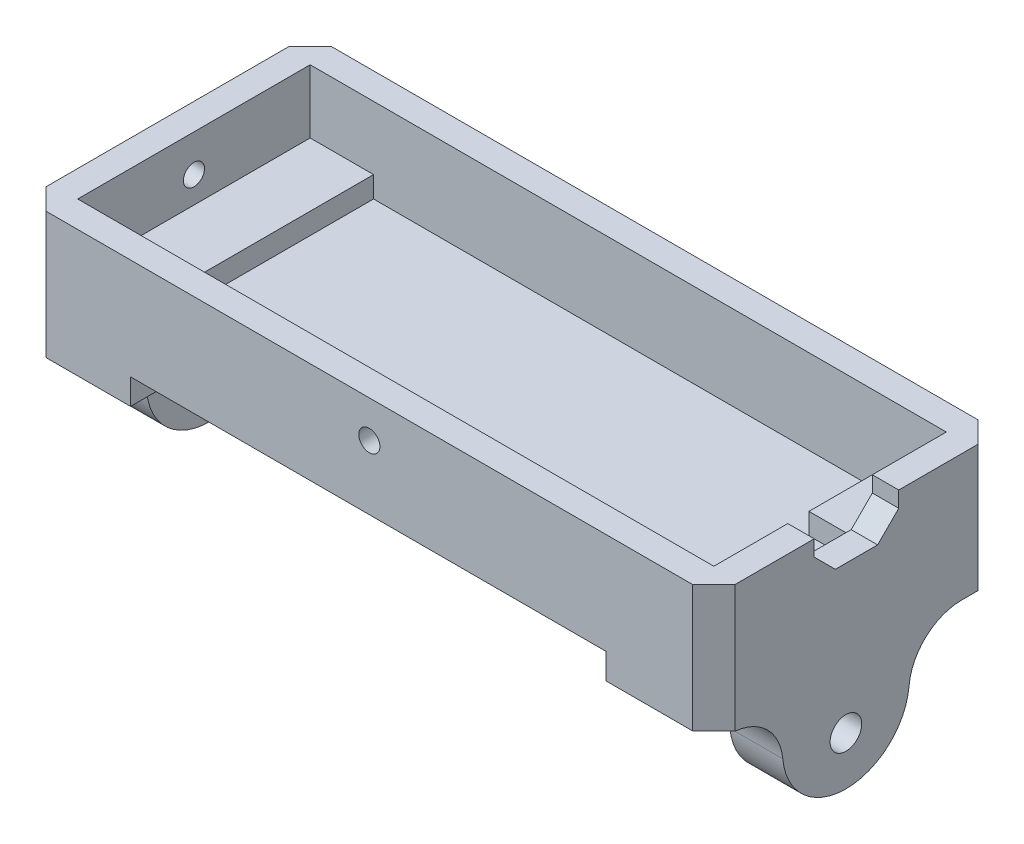
SolidWorks part; units mm, degrees
ref_plane "Front Plane" through (0, 0, 0) normal (0, 0, 1) x (1, 0, 0)
ref_plane "Top Plane" through (0, 0, 0) normal (0, 1, 0) x (1, 0, 0)
ref_plane "Right Plane" through (0, 0, 0) normal (1, 0, 0) x (0, 0, -1)
sketch "Sketch1" plane through (0, 0, 0) normal (0, 1, 0) x (1, 0, 0)
  line L0 (-19, 11.7194) -> (-29, 6.7194)
  line L1 (-19, 11.7194) -> (-10, 11.7194)
  line L2 (-29, 6.7194) -> (-29, -3.2806)
  line L3 (-19, -9.2806) -> (21, -9.2806)
  line L4 (29, 7.4633) -> (29, -6.3504)
  line L5 (-19, -9.2806) -> (-29, -3.2806)
  line L6 (-10, 11.7194) -> (-9.4845, 10.9718)
  line L7 (-9.0728, 10.7556) -> (-6.9671, 10.7556)
  line L8 (-6.5657, 10.9575) -> (-6, 11.7194)
  line L9 (-6, 11.7194) -> (19, 11.7194)
  line L10 (19, 11.7194) -> (19, 4.7194)
  line L11 (23, 4.7194) -> (23, 8.7194)
  line L12 (23, 8.7194) -> (27.7439, 8.7194)
  line L13 (27.7439, 8.7194) -> (29, 7.4633)
  line L14 (29, -6.3504) -> (21, -9.2806)
  line L15 (-29.7, 12.2194) -> (30.5, 12.2194)
  line L16 (-30.2, 14.7194) -> (31, 14.7194)
  line L17 (-32.2, 12.7194) -> (-32.2, -10.2806)
  line L18 (-30.2, -12.2806) -> (31, -12.2806)
  line L19 (33, 12.7194) -> (33, -10.2806)
  line L20 (30.5, 12.2194) -> (30.5, -9.7806)
  line L21 (-29.7, -9.7806) -> (30.5, -9.7806)
  line L22 (-29.7, 12.2194) -> (-29.7, -9.7806)
  line L23 (-30.2, -12.2806) -> (-32.2, -10.2806)
  line L24 (-32.2, 12.7194) -> (-30.2, 14.7194)
  line L25 (31, 14.7194) -> (33, 12.7194)
  line L26 (31, -12.2806) -> (33, -10.2806)
  arc A0 (-6.9671, 10.7556) -> (-6.5657, 10.9575) centre (-6.9671, 11.2556) ccw
  arc A1 (-9.4845, 10.9718) -> (-9.0728, 10.7556) centre (-9.0728, 11.2556) ccw
  arc A2 (19, 4.7194) -> (23, 4.7194) centre (21, 4.7194) ccw
  arc A7 (30.5, 12.2194) -> (30.5, 12.2194) centre (30.5, 12.2194) cw
  arc A8 (30.5, -9.7806) -> (30.5, -9.7806) centre (30.5, -9.7806) ccw
  arc A9 (-29.7, -9.7806) -> (-29.7, -9.7806) centre (-29.7, -9.7806) ccw
  arc A10 (-29.7, 12.2194) -> (-29.7, 12.2194) centre (-29.7, 12.2194) ccw
  arc A11 (-32.2, -10.2806) -> (-30.2, -12.2806) centre (-30.2, -10.2806) ccw construction
  arc A12 (-30.2, 14.7194) -> (-32.2, 12.7194) centre (-30.2, 12.7194) ccw construction
  arc A13 (31, -12.2806) -> (33, -10.2806) centre (31, -10.2806) ccw construction
  arc A14 (31, 14.7194) -> (33, 12.7194) centre (31, 12.7194) cw construction
  point P0 (0, 3.1087)
  point P7 (-10, 11.7194)
  point P8 (-6, 11.7194)
  point P17 (19, 11.7194)
  dimension "D7" = 0.5
  dimension "D1" = 10
  dimension "D2" = 5
  dimension "D3" = 10
  dimension "D4" = 3.2
  dimension "D5" = 4
  dimension "D6" = 9
  dimension "D8" = 25
  dimension "D9" = 7
  dimension "D10" = 4
  dimension "D11" = 4
  dimension "D12" = 21
  dimension "D13" = 4
  dimension "D14" = 3
  dimension "D15" = 3
  dimension "D17" = 2.5
extrude "Boss-Extrude1" add sketch "Sketch1" along normal blind 10 contours L16 L24 L17 L23 L18 L26 L19 L25 L22 L15 L20 L21 region at (0.4, 0, -14.0137)
extrude "Boss-Extrude2" add sketch "Sketch1<3>" along normal blind 2 contours L15 L22 L21 L20 L10 A2 L11 L12 L13 L4 L14 L3 L5 L2 L0 L1 L6 A1 L7 A0 L8 L9 | A2 L10 L9 L8 A0 L7 A1 L6 L1 L0 L2 L5 L3 L14 L4 L13 L12 L11 region at (-0.075, 0, -0.9762) region at (0.4, 0, -12.1553)
sketch "Sketch1<3>" plane through (0, 0, 0) normal (0, 1, 0) x (1, 0, 0) same geometry as "Sketch1"
sketch "Sketch2" plane through (0, 2, 0) normal (0, 1, 0) x (1, 0, 0)
  line L0 (-29.7, -9.7806) -> (30.5, -9.7806) construction
  line L1 (-29.7, 12.2194) -> (-23.7, 12.2194)
  line L2 (-29.7, 12.2194) -> (-29.7, -9.7806)
  line L3 (-29.7, -9.7806) -> (-23.7, -9.7806)
  line L4 (-23.7, 12.2194) -> (-23.7, -9.7806)
  line L5 (-29.7, -9.7806) -> (30.5, -9.7806) construction
  line L6 (30.5, 12.2194) -> (24.5, 12.2194)
  line L7 (30.5, 12.2194) -> (30.5, -9.7806)
  line L8 (30.5, -9.7806) -> (24.5, -9.7806)
  line L9 (24.5, 12.2194) -> (24.5, -9.7806)
  dimension "D1" = 6
  dimension "D2" = 6
extrude "Boss-Extrude3" add sketch "Sketch2" along normal blind 2
sketch "Sketch3" plane through (0, 0, 0) normal (0, -1, 0) x (1, 0, 0)
  line L0 (-30.2, 12.2806) -> (31, 12.2806) construction
  line L1 (-32.2, 14.2806) -> (36, 14.2806)
  line L2 (-37.2, 9.2806) -> (-37.2, -11.7194)
  line L3 (-32.2, -16.7194) -> (36, -16.7194)
  line L4 (41, 9.2806) -> (41, -11.7194)
  line L5 (-30.2, -14.7194) -> (31, -14.7194) construction
  line L6 (-32.2, -12.7194) -> (-32.2, 10.2806) construction
  line L7 (33, -12.7194) -> (33, 10.2806) construction
  line L8 (-37.2, 9.2806) -> (-32.2, 14.2806)
  line L9 (-37.2, -11.7194) -> (-32.2, -16.7194)
  line L10 (36, 14.2806) -> (41, 9.2806)
  line L11 (36, -16.7194) -> (41, -11.7194)
  point P0 (-37.2, 14.2806)
  point P1 (41, -16.7194)
  point P2 (-37.2, -16.7194)
  point P3 (41, 14.2806)
  dimension "D1" = 2
  dimension "D2" = 2
  dimension "D3" = 5
  dimension "D4" = 8
extrude "Boss-Extrude4" add sketch "Sketch3" along normal blind 2
fillet "Fillet1" radius 0.5 2 edges at (32, 0, -13.7194) (0.4, 0, -14.7194)
sketch "Sketch4" plane through (33, 0, 0) normal (1, 0, 0) x (0, 0, -1)
  line L0 (12.7194, 10) -> (-10.2806, 10) construction
  line L1 (-2.7806, 10) -> (5.2194, 10)
  line L2 (-2.7806, 10) -> (-2.7806, 8.5)
  line L3 (-0.7806, 6.5) -> (3.2194, 6.5)
  line L4 (5.2194, 10) -> (5.2194, 8.5)
  line L7 (-2.7806, 8.5) -> (-0.7806, 6.5)
  line L8 (3.2194, 6.5) -> (5.2194, 8.5)
  line L9 (-12.2806, 10) -> (14.7194, 10) construction
  line L10 (14.7194, 10) -> (12.7194, 10) construction
  line L11 (-12.2806, 10) -> (-12.2806, 0) construction
  point P1 (5.2194, 6.5)
  point P2 (-2.7806, 6.5)
  dimension "D2" = 8
  dimension "D3" = 3.5
  dimension "D4" = 9.5
extrude "Cut-Extrude1" cut sketch "Sketch4" against normal blind 10.5
sketch "Sketch5" plane through (0, 0, 0) normal (0, 1, 0) x (-1, 0, 0)
  line L0 (-40.124, 15.07) -> (-40.124, -12.93) construction
  line L1 (-33, 13.7806) -> (-38, 13.7806)
  line L2 (-33, 13.7806) -> (-33, 4.7806)
  line L3 (-33, 4.7806) -> (-38, 4.7806)
  line L4 (-38, 13.7806) -> (-38, 4.7806)
  line L5 (-33, -14.2194) -> (-38, -14.2194)
  line L6 (-33, -14.2194) -> (-33, -5.2194)
  line L7 (-33, -5.2194) -> (-38, -5.2194)
  line L8 (-38, -14.2194) -> (-38, -5.2194)
  line L10 (-36, 14.2806) -> (32.2, 14.2806) construction
  line L11 (-33, 2.7806) -> (-33, 10.2806) construction
  line L12 (-33, -13.4265) -> (-33, 10.2806) construction
  point P12 (-36, 14.2806)
  dimension "D1" = 9
  dimension "D2" = 28
  dimension "D3" = 9
  dimension "D4" = 5
  dimension "D5" = 5
  dimension "D6" = 28
  dimension "D7" = 31
  dimension "D8" = 0.5
extrude "Boss-Extrude5" add sketch "Sketch5" along normal blind 5
sketch "Sketch7" plane through (38, 0, 0) normal (1, 0, 0) x (0, 0, -1)
  line L1 (-13.7806, 5) -> (-10.2806, 5)
  line L2 (-13.7806, 5) -> (-13.7806, 0)
  line L3 (-13.7806, 0) -> (-10.2806, 0)
  line L4 (-10.2806, 5) -> (-10.2806, 0)
  line L5 (15.2194, 5) -> (12.7194, 5)
  line L6 (15.2194, 5) -> (15.2194, 0)
  line L7 (15.2194, 0) -> (12.7194, 0)
  line L8 (12.7194, 5) -> (12.7194, 0)
extrude "Cut-Extrude3" cut sketch "Sketch7" against normal blind 5
sketch "Sketch10" plane through (0, 0, -12.7194) normal (0, 0, -1) x (-1, 0, 0)
  line L0 (-35.5, 5) -> (-35.5, 2.5) construction
  line L5 (-38, 5) -> (-33, 5)
  line L6 (-38, 5) -> (-38, 0)
  line L7 (-38, 0) -> (-33, 0)
  line L8 (-33, 5) -> (-33, 0)
  line L9 (-35.5, 2.5) -> (-38, 2.5) construction
  circle A0 centre (-35.5, 2.5) radius 1.5
  circle A1 centre (-35.5, 2.5) radius 2.5
  line M1 (-38, 5) -> (-38, 0)
  line M2 (-38, 0) -> (-33, 0)
  dimension "D1" = 3
extrude "Cut-Extrude4" cut sketch "Sketch10" against normal up to surface (23 mm away) contours A0 L5 M1 | A0 L6 M2 region at (37.4416, 4.4416, -12.7194) region at (37.4416, 0.5584, -12.7194) up to face at (35.5, 2.5, 10.2806)
sketch "Sketch11" plane through (0, 0, -12.7194) normal (0, 0, -1) x (-1, 0, 0)
  circle A0 centre (-35.5, 2.5) radius 1.5
  dimension "D1" = 3
extrude "Cut-Extrude5" cut sketch "Sketch11" against normal up to surface (23 mm away) up to face at (34.875, 2.5, 10.2806)
sketch "Sketch12" plane through (-32.2, 0, 0) normal (-1, 0, 0) x (0, 0, 1)
  line L0 (14.2806, -2) -> (14.2806, 2.4239)
  line L1 (14.2806, 2.4239) -> (9.8567, -2)
  line L2 (14.2806, -2) -> (9.2806, -2) construction
  line L3 (9.8567, -2) -> (14.2806, -2)
  line L4 (-1.2194, -2) -> (-1.2194, 8.8282) construction
  line L5 (9.2806, -2) -> (-11.7194, -2) construction
  line L6 (-12.2955, -2) -> (-16.7194, -2)
  line L7 (-16.7194, -2) -> (-16.7194, 2.4239)
  line L8 (-16.7194, 2.4239) -> (-12.2955, -2)
extrude "Cut-Extrude6" cut sketch "Sketch12" against normal blind 45 from offset 10 offset against normal yes
sketch "Sketch13" plane through (0, 4, 0) normal (0, 1, 0) x (1, 0, 0)
  line L0 (24.5, 12.2194) -> (24.5, -9.7806) construction
  line L1 (30.5, 5.2194) -> (24.5, 5.2194)
  line L2 (30.5, 5.2194) -> (30.5, -2.8008)
  line L3 (30.5, -2.8008) -> (24.5, -2.8008)
  line L4 (24.5, 5.2194) -> (24.5, -2.8008)
extrude "Cut-Extrude7" cut sketch "Sketch13" against normal up to surface (2 mm away) up to face at (0.4, 2, -1.2194)
sketch "Sketch19" plane through (-32.2, 0, 0) normal (-1, 0, 0) x (0, 0, 1)
  line L0 (-12.7194, 0) -> (10.2806, 0) construction
  circle A0 centre (-1.2194, 6.5) radius 1
  dimension "D1" = 2
  dimension "D2" = 6.5
extrude "Cut-Extrude9" cut sketch "Sketch19" against normal blind 6
sketch "Sketch20" plane through (0, 0, 12.2806) normal (0, 0, 1) x (1, 0, 0)
  line L0 (-22.2, 0.4239) -> (22.8, 0.4239) construction
  line L1 (0.4, 10) -> (0.4, 3.6445) construction
  line L2 (-30.2, 10) -> (31, 10) construction
  circle A0 centre (0.4, 6.5039) radius 1
  dimension "D1" = 2
  dimension "D2" = 6.08
extrude "Cut-Extrude10" cut sketch "Sketch20" against normal blind 6
sketch "Sketch21" plane through (0, 0, 0) normal (0, 1, 0) x (1, 0, 0)
  line L0 (33, 12.7194) -> (33, -10.2806)
  line L1 (41, 11.7194) -> (41, -9.2806)
  line L2 (22.8, 15.2194) -> (22.8, 14.7245)
  line L3 (22.8, 14.7245) -> (31, 14.7194)
  line L4 (31, 14.7194) -> (33, 12.7194)
  line L5 (-22.2, 15.2194) -> (-22.2, 14.7245)
  line L6 (-22.2, 14.7245) -> (-30.2, 14.7194)
  line L12 (-22.2, -14.2806) -> (-22.2, -12.2806)
  line L13 (-22.2, -12.2806) -> (-30.2, -12.2806)
  line L14 (-22.2, -12.2806) -> (-30.2, -12.2806)
  line L15 (-30.2, -12.2806) -> (-32.2, -10.2806)
  line L16 (-30.2, -12.2806) -> (-32.2, -10.2806)
  line L17 (-32.2, -10.2806) -> (-32.2, 12.7194)
  line L18 (-22.2, 15.2194) -> (-22.2, 16.7194)
  line L19 (-22.2, 16.7194) -> (-32.2, 16.7194)
  line L20 (-32.2, 16.7194) -> (-37.2, 11.7194)
  line L21 (-37.2, 11.7194) -> (-37.2, -9.2806)
  line L22 (-37.2, -9.2806) -> (-32.2, -14.2806)
  line L23 (-32.2, -14.2806) -> (-22.2, -14.2806)
  line L24 (-22.2, -14.2806) -> (-22.2, -12.2806)
  line L30 (-22.2, 15.2194) -> (-22.2, 16.7194)
  line L31 (-22.2, 16.7194) -> (-32.2, 16.7194)
  line L32 (-32.2, 16.7194) -> (-37.2, 11.7194)
  line L33 (-37.2, 11.7194) -> (-37.2, -9.2806)
  line L34 (-37.2, -9.2806) -> (-32.2, -14.2806)
  line L35 (-32.2, -14.2806) -> (-22.2, -14.2806)
  line L43 (31, -12.2806) -> (22.8, -12.2806)
  line L44 (22.8, -12.2806) -> (22.8, -14.2806)
  line L45 (22.8, -14.2806) -> (36, -14.2806)
  line L46 (36, -14.2806) -> (41, -9.2806)
  line L47 (41, -9.2806) -> (41, 11.7194)
  line L48 (41, 11.7194) -> (36, 16.7194)
  line L49 (36, 16.7194) -> (22.8, 16.7194)
  line L50 (22.8, 16.7194) -> (22.8, 15.2194)
  line L51 (31, -12.2806) -> (22.8, -12.2806)
  line L52 (22.8, 15.2194) -> (31.2071, 15.2194)
  line L53 (31.2071, 15.2194) -> (33, 13.4265)
  line L54 (33, 13.4265) -> (33, 12.7194)
  line L55 (33, 12.7194) -> (35.5, 12.7194)
  line L56 (35.5, 12.7194) -> (35.5, 5.2194)
  line L58 (35.5, 5.2194) -> (33, 5.2194)
  line L59 (33, 5.2194) -> (33, -4.7806)
  line L60 (33, 5.2194) -> (33, -4.7806)
  line L61 (33, -4.7806) -> (35.5, -4.7806)
  line L63 (22.8, -12.2806) -> (22.8, -14.2806)
  line L64 (22.8, -14.2806) -> (36, -14.2806)
  line L65 (36, -14.2806) -> (41, -9.2806)
  line L67 (41, 11.7194) -> (36, 16.7194)
  line L68 (36, 16.7194) -> (22.8, 16.7194)
  line L69 (22.8, 16.7194) -> (22.8, 15.2194)
  line L81 (-32.2, -10.2806) -> (-32.2, 12.7194)
  line L82 (-32.2, 12.7194) -> (-29.7, 15.2194)
  line L83 (-32.2, 12.7194) -> (-29.7, 15.2194)
  line L84 (-29.7, 15.2194) -> (-22.2, 15.2194)
  line L92 (35.5, -4.7806) -> (35.5, -10.2806)
  line L93 (35.5, -10.2806) -> (33, -10.2806)
  line L94 (33, -10.2806) -> (31, -12.2806)
  line L95 (33, -10.2806) -> (31, -12.2806)
  line M32 (-22.2, -14.2806) -> (-22.2, -12.2806)
  line M33 (-22.2, -12.2806) -> (-30.2, -12.2806)
  line M34 (-30.2, -12.2806) -> (-32.2, -10.2806)
  line M35 (-32.2, -10.2806) -> (-32.2, 12.7194)
  line M36 (-32.2, 12.7194) -> (-29.7, 15.2194)
  line M37 (-29.7, 15.2194) -> (-22.2, 15.2194)
  line M38 (-22.2, 15.2194) -> (-22.2, 16.7194)
  line M39 (-22.2, 16.7194) -> (-32.2, 16.7194)
  line M40 (-32.2, 16.7194) -> (-37.2, 11.7194)
  line M41 (-37.2, 11.7194) -> (-37.2, -9.2806)
  line M42 (-37.2, -9.2806) -> (-32.2, -14.2806)
  line M43 (-32.2, -14.2806) -> (-22.2, -14.2806)
  dimension "D1" = 0
  dimension "D2" = 0
extrude "Cut-Extrude13" cut sketch "Sketch21" against normal blind 23 and the other way blind 23 contours M43 M32 M33 M34 M35 M36 M37 M38 M39 M40 M41 M42 | L6 L5 M37 M36 | L0 L95 L51 L63 L64 L65 L1 L67 L68 L69 L2 L3 L4 region at (34.25, 0, -8.9694) region at (28.2069, 0, -14.7374) region at (35.6486, 0, -0.7875) region at (34.25, 0, 7.5306) region at (-32.9361, 0, -0.9063) region at (-26.0827, 0, -14.968)
sketch "Sketch24" plane through (0, -2, 0) normal (0, -1, 0) x (1, 0, 0)
  line L0 (-32.2, -0.2194) -> (33, -0.2194) construction
  line L1 (33, 10.2806) -> (33, -12.7194) construction
  line L2 (-32.2, -12.7194) -> (-32.2, 10.2806) construction
  line L3 (-32.2, 5.7806) -> (-27.2, 5.7806)
  line L4 (-32.2, 5.7806) -> (-32.2, -6.2194)
  line L5 (-32.2, -6.2194) -> (-27.2, -6.2194)
  line L6 (-27.2, 5.7806) -> (-27.2, -6.2194)
  line L8 (33, 5.7806) -> (28, 5.7806)
  line L9 (33, 5.7806) -> (33, -6.2194)
  line L10 (33, -6.2194) -> (28, -6.2194)
  line L11 (28, 5.7806) -> (28, -6.2194)
  dimension "D1" = 65.2
  dimension "D2" = 5
  dimension "D3" = 5
  dimension "D4" = 12
  dimension "D5" = 6
  dimension "D6" = 6
  dimension "D7" = 12
extrude "Boss-Extrude6" add sketch "Sketch24" along normal blind 10
fillet "Fillet2" radius 6 4 edges at (30.5, -12, -6.2194) (30.5, -12, 5.7806) (-29.7, -12, 5.7806) (-29.7, -12, -6.2194)
sketch "Sketch25" plane through (-32.2, 0, 0) normal (-1, 0, 0) x (0, 0, 1)
  line L0 (-0.2194, -12) -> (-0.2194, -3.1317) construction
  circle A0 centre (-0.2194, -7.409) radius 1.5
  dimension "D1" = 3
extrude "Cut-Extrude14" cut sketch "Sketch25" against normal through all
fillet "Fillet3" radius 5 4 edges at (30.5, -2, 5.7806) (-29.7, -2, 5.7806) (-29.7, -2, -6.2194) (30.5, -2, -6.2194)
sketch "Sketch26" plane through (0, 10, 0) normal (0, 1, 0) x (1, 0, 0)
  line L16 (33, -2.7806) -> (30.5, -2.7806)
  line L17 (30.5, -2.7806) -> (30.5, -9.7806)
  line L18 (30.5, -9.7806) -> (-29.7, -9.7806)
  line L19 (-29.7, -9.7806) -> (-29.7, 12.2194)
  line L20 (-29.7, 12.2194) -> (30.5, 12.2194)
  line L21 (30.5, 12.2194) -> (30.5, 5.2194)
  line L22 (30.5, 5.2194) -> (33, 5.2194)
  line L23 (33, 5.2194) -> (33, 12.7194)
  line L24 (33, 12.7194) -> (31, 14.7194)
  line L25 (31, 14.7194) -> (-30.2, 14.7194)
  line L26 (-30.2, 14.7194) -> (-32.2, 12.7194)
  line L27 (-32.2, 12.7194) -> (-32.2, -10.2806)
  line L28 (-32.2, -10.2806) -> (-30.2, -12.2806)
  line L29 (-30.2, -12.2806) -> (31, -12.2806)
  line L30 (31, -12.2806) -> (33, -10.2806)
  line L31 (33, -10.2806) -> (33, -2.7806)
  line L32 (33, -2.7806) -> (30.5, -2.7806)
  line L33 (30.5, -2.7806) -> (30.5, -9.7806)
  line L34 (30.5, -9.7806) -> (-29.7, -9.7806)
  line L35 (-29.7, -9.7806) -> (-29.7, 12.2194)
  line L36 (-29.7, 12.2194) -> (30.5, 12.2194)
  line L37 (30.5, 12.2194) -> (30.5, 5.2194)
  line L38 (30.5, 5.2194) -> (33, 5.2194)
  line L39 (33, 5.2194) -> (33, 12.7194)
  line L40 (33, 12.7194) -> (31, 14.7194)
  line L41 (31, 14.7194) -> (-30.2, 14.7194)
  line L42 (-30.2, 14.7194) -> (-32.2, 12.7194)
  line L43 (-32.2, 12.7194) -> (-32.2, -10.2806)
  line L44 (-32.2, -10.2806) -> (-30.2, -12.2806)
  line L45 (-30.2, -12.2806) -> (31, -12.2806)
  line L46 (31, -12.2806) -> (33, -10.2806)
  line L47 (33, -10.2806) -> (33, -2.7806)
  dimension "D1" = 0
